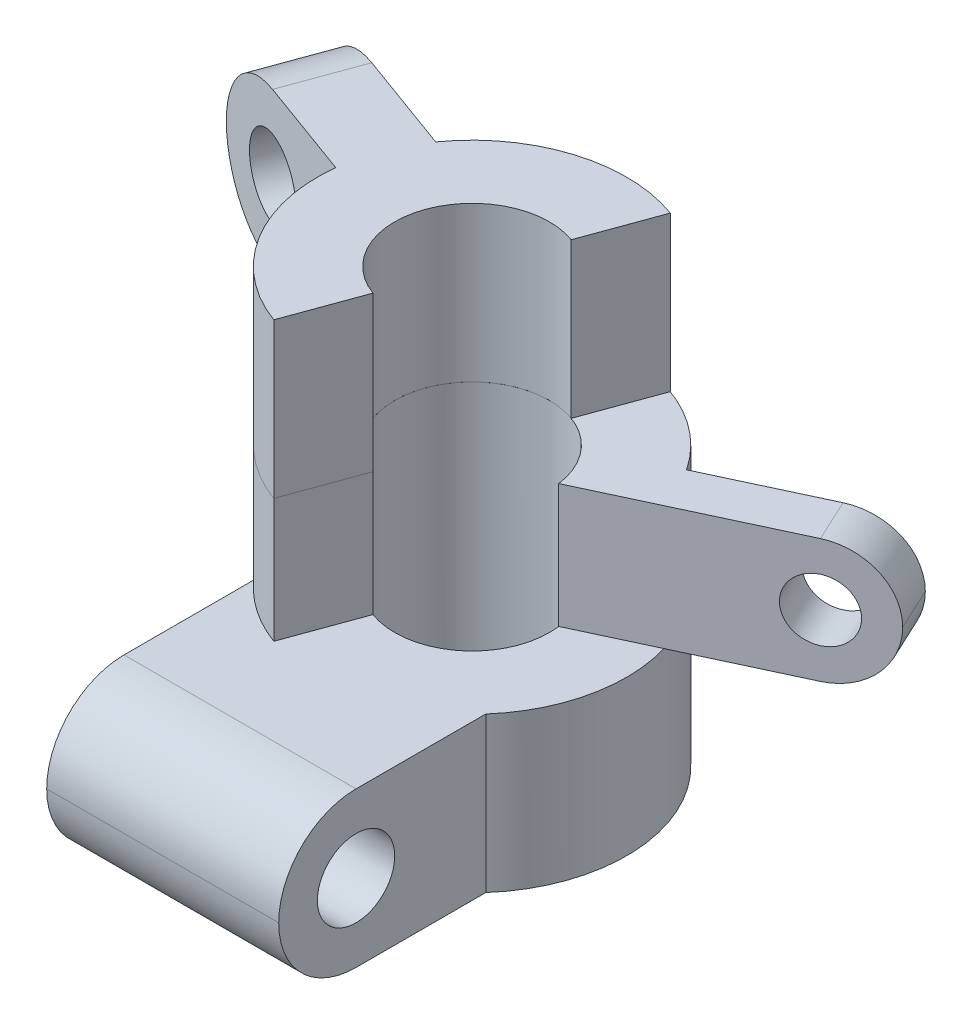
SolidWorks part; units mm, degrees
ref_plane "前视基准面" through (0, 0, 0) normal (0, 0, 1) x (1, 0, 0)
ref_plane "上视基准面" through (0, 0, 0) normal (0, 1, 0) x (1, 0, 0)
ref_plane "右视基准面" through (0, 0, 0) normal (1, 0, 0) x (0, 0, -1)
other "Configuration Table"
sketch "草图1" plane through (0, 0, 0) normal (0, 1, 0) x (1, 0, 0)
  line L0 (0, 0) -> (0, 26.7712)
  line L1 (0, 0) -> (30, 0)
  line L2 (15, -18.9264) -> (15, 63.9933) construction
  line L3 (30, 0) -> (30, 26.7712)
  circle A3 centre (15, 40) radius 20
  circle A4 centre (15, 40) radius 10
  dimension "D1" = 40
  dimension "D2" = 30
extrude "凸台-拉伸4" add sketch "草图1" along normal blind 20 contours L2 A3 A4 | A3 L2 A4 | L1 L2 A3 L0 | L2 L1 L3 A3 region at (7.134, 0, -11.1253) region at (-2.8211, 0, -48.0448) region at (22.866, 0, -11.1253) region at (28.8259, 0, -53.8259)
fillet "圆角2" radius 10 2 edges at (15, 0, 0) (15, 20, 0)
sketch "草图5" plane through (0, 0, 0) normal (-1, 0, 0) x (0, 0, 1)
  circle A0 centre (-10, 10) radius 5
  arc A1 (0, 10) -> (-10, 20) centre (-10, 10) ccw construction
extrude "切除-拉伸1" cut sketch "草图5" against normal through all contours A0
sketch "草图7" plane through (0, 20, 0) normal (0, 1, 0) x (1, 0, 0)
  line L0 (30, 26.7712) -> (30, 10) construction
  line L1 (30, 10) -> (0, 10) construction
  line L2 (0, 10) -> (0, 26.7712) construction
  line L3 (0, 26.7712) -> (0, 10) construction
  line L4 (0, 10) -> (30, 10) construction
  line L5 (30, 10) -> (30, 26.7712) construction
  line L6 (30, 26.7712) -> (30, 10)
  line L7 (30, 10) -> (0, 10)
  line L8 (0, 10) -> (0, 26.7712)
  line L9 (0, 26.7712) -> (0, 10)
  line L10 (0, 10) -> (30, 10)
  line L11 (30, 10) -> (30, 26.7712)
  line L12 (15, 40) -> (15, 60)
  line L13 (8.1596, 21.2061) -> (11.5798, 30.6031)
  line L14 (18.4202, 49.3969) -> (21.8404, 58.7939)
  line L15 (18.4202, 49.3969) -> (21.8404, 58.7939)
  line L16 (-27.1169, 50.3492) -> (-23.6967, 59.7461)
  line L17 (-27.1169, 50.3492) -> (-4.8727, 42.253)
  line L18 (-23.6967, 59.7461) -> (-1.2971, 51.5933)
  arc A0 (30, 26.7712) -> (0, 26.7712) centre (15, 40) ccw construction
  arc A1 (30, 26.7712) -> (0, 26.7712) centre (15, 40) ccw construction
  arc A2 (30, 26.7712) -> (0, 26.7712) centre (15, 40) ccw
  arc A3 (30, 26.7712) -> (0, 26.7712) centre (15, 40) ccw
  circle A4 centre (15, 40) radius 10 construction
  arc A5 (21.8404, 58.7939) -> (8.1596, 21.2061) centre (15, 40) ccw
  arc A6 (18.4202, 49.3969) -> (11.5798, 30.6031) centre (15, 40) ccw
  point P17 (-25.4068, 55.0477)
  circle M1 centre (15, 40) radius 10
  arc M5 (30, 26.7712) -> (0, 26.7712) centre (15, 40) ccw
  dimension "D1" = 20
extrude "凸台-拉伸6" add sketch "草图7" along normal blind 20 from offset 16 separate body contours L14 L12 M1 M5 | A5 L13 L12 M5 M1 | L18 L16 L17 M5 region at (17.6875, 20, -55.2416) region at (4.1951, 20, -41.9052) region at (-14.4427, 20, -51.0633)
fillet "圆角3" radius 10 2 edges at (-25.4068, 36, -55.0477) (-25.4068, 56, -55.0477)
sketch "草图9" plane through (13.0098, 0, -35.7443) normal (-0.342, 0, 0.9397) x (0.9397, 0, 0.342)
  circle A0 centre (-32.702, 46) radius 5
  arc A1 (-32.702, 56) -> (-42.702, 46) centre (-32.702, 46) ccw construction
extrude "切除-拉伸2" cut sketch "草图9" against normal through all contours A0
sketch "草图10" plane through (0, 20, 0) normal (0, 1, 0) x (1, 0, 0)
  line L5 (-1.2971, 51.5933) -> (-14.2998, 56.3259)
  line L6 (-14.2998, 56.3259) -> (-17.72, 46.929)
  line L7 (-17.72, 46.929) -> (-4.8727, 42.253)
  line L8 (8.1596, 21.2061) -> (11.5798, 30.6031)
  line L9 (18.4202, 49.3969) -> (21.8404, 58.7939)
  line L10 (-1.2971, 51.5933) -> (-14.2998, 56.3259)
  line L11 (-14.2998, 56.3259) -> (-17.72, 46.929)
  line L12 (-17.72, 46.929) -> (-4.8727, 42.253)
  line L13 (8.1596, 21.2061) -> (11.5798, 30.6031)
  line L14 (18.4202, 49.3969) -> (21.8404, 58.7939)
  arc A3 (-4.8727, 42.253) -> (8.1596, 21.2061) centre (15, 40) ccw
  arc A4 (18.4202, 49.3969) -> (11.5798, 30.6031) centre (15, 40) ccw
  arc A5 (21.8404, 58.7939) -> (-1.2971, 51.5933) centre (15, 40) ccw
  arc A6 (-4.8727, 42.253) -> (8.1596, 21.2061) centre (15, 40) ccw
  arc A7 (18.4202, 49.3969) -> (11.5798, 30.6031) centre (15, 40) ccw
  arc A8 (21.8404, 58.7939) -> (-1.2971, 51.5933) centre (15, 40) ccw
  dimension "D1" = 0
sketch "草图11" plane through (0, 20, 0) normal (0, 1, 0) x (1, 0, 0)
  line L0 (18.4202, 49.3969) -> (15, 40)
  line L1 (15, 40) -> (49.3963, 27.4808)
  line L2 (15, 40) -> (53.9712, 58.1726)
  line L3 (52.6945, 60.9105) -> (55.248, 55.4346)
  line L4 (55.248, 55.4346) -> (17.2303, 37.7067)
  line L5 (52.6945, 60.9105) -> (31.6415, 51.0933)
  line L6 (15, 40) -> (21.8404, 58.7939)
  arc A0 (30, 26.7712) -> (0, 26.7712) centre (15, 40) ccw construction
  arc A1 (21.8404, 58.7939) -> (34.1949, 45.6174) centre (15, 40) cw
  arc A2 (18.4202, 49.3969) -> (24.9163, 41.2908) centre (15, 40) cw
  circle A3 centre (15, 40) radius 10 construction
  point P12 (53.9712, 58.1726)
  dimension "D1" = 45
  dimension "D2" = 43
extrude "凸台-拉伸7" add sketch "草图11" along normal blind 16 contours L3 L5 A0 L2 | L4 L3 L2 A0 | L4 A0 L2 | L6 L4 L2 A0 region at (25.2411, 20, -51.1763) region at (29.1303, 20, -44.9159) region at (42.8746, 20, -54.6675) region at (44.1534, 20, -51.9251)
fillet "圆角4" radius 8 2 edges at (53.9712, 20, -58.1726) (53.9712, 36, -58.1726)
sketch "草图13" plane through (-13.9185, 0, -29.8484) normal (-0.4226, 0, -0.9063) x (-0.9063, 0, 0.4226)
  circle A0 centre (-65.4993, 28) radius 4
  arc A1 (-65.4993, 36) -> (-73.4993, 28) centre (-65.4993, 28) ccw construction
extrude "切除-拉伸3" cut sketch "草图13" against normal through all contours A0
sketch "草图15" plane through (0, 20, 0) normal (0, 1, 0) x (1, 0, 0)
  line L0 (11.5798, 30.6031) -> (8.1596, 21.2061)
  line L1 (21.8404, 58.7939) -> (18.4202, 49.3969)
  arc A0 (8.1596, 21.2061) -> (21.8404, 58.7939) centre (15, 40) cw
  arc A1 (18.4202, 49.3969) -> (11.5798, 30.6031) centre (15, 40) ccw
extrude "凸台-拉伸8" add sketch "草图15" along normal blind 16
